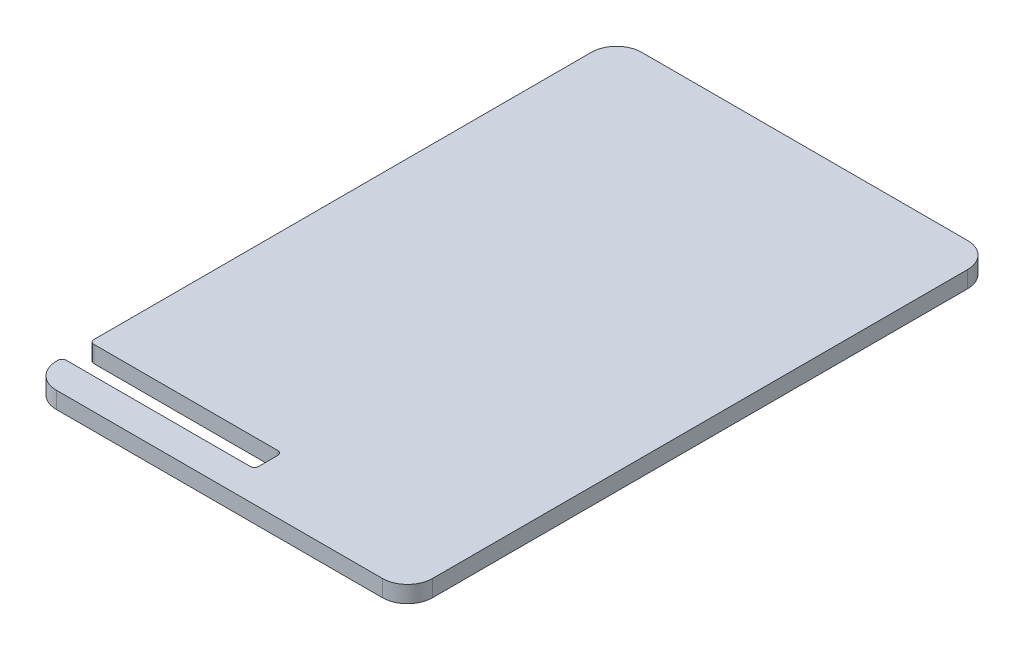
SolidWorks part; units mm, degrees
ref_plane "Alzado" through (0, 0, 0) normal (0, 0, 1) x (1, 0, 0)
ref_plane "Planta" through (0, 0, 0) normal (0, 1, 0) x (1, 0, 0)
ref_plane "Vista lateral" through (0, 0, 0) normal (1, 0, 0) x (0, 0, -1)
sketch "Croquis1" plane through (0, 0, 0) normal (0, 1, 0) x (1, 0, 0)
  line L1 (-22.5, 35.3062) -> (22.5, 35.3062)
  line L2 (-22.5, 35.3062) -> (-22.5, -34.6938)
  line L3 (-22.5, -34.6938) -> (22.5, -34.6938)
  line L4 (22.5, 35.3062) -> (22.5, -34.6938)
  dimension "D1" = 22.5
  dimension "D2" = 45
  dimension "D3" = 35.3062
  dimension "D4" = 70
extrude "Saliente-Extruir1" add sketch "Croquis1" along normal blind 2
sketch "Croquis2" plane through (0, 2, 0) normal (0, 1, 0) x (1, 0, 0)
  line L0 (-22.5, 35.3062) -> (-22.5, -34.6938) construction
  line L1 (-22.5, -27.7) -> (0.5, -27.7)
  line L2 (-22.5, -27.7) -> (-22.5, -31)
  line L3 (-22.5, -31) -> (0.5, -31)
  line L4 (0.5, -27.7) -> (0.5, -31)
  dimension "D1" = 3.3
  dimension "D2" = 31
  dimension "D3" = 23
extrude "Cortar-Extruir1" cut sketch "Croquis2" against normal up to surface (2 mm away) up to face at (0, 0, -0.3062)
fillet "Redondeo1" radius 3 4 edges at (-22.5, 1, 34.6938) (22.5, 1, 34.6938) (-22.5, 1, -35.3062) (22.5, 1, -35.3062)
fillet "Redondeo2" radius 0.5 4 edges at (-22.5, 1, 31) (0.5, 1, 31) (0.5, 1, 27.7) (-22.5, 1, 27.7)
